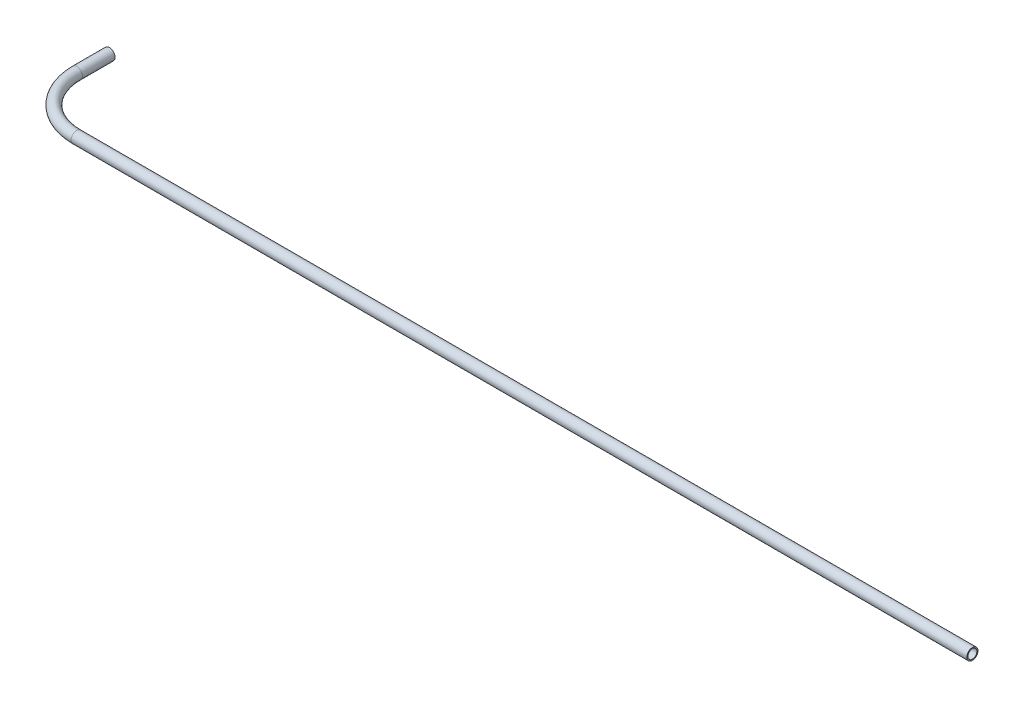
SolidWorks part; units mm, degrees
ref_plane "Front Plane" through (0, 0, 0) normal (0, 0, 1) x (1, 0, 0)
ref_plane "Top Plane" through (0, 0, 0) normal (0, 1, 0) x (1, 0, 0)
ref_plane "Right Plane" through (0, 0, 0) normal (1, 0, 0) x (0, 0, -1)
ref_axis "Axis1" through (-5.3297, 0, 0) along (1, 0, 0)
sketch "Sketch1" plane through (0, 0, 0) normal (1, 0, 0) x (0, 0, -1)
  circle A0 centre (0, 0) radius 0.2032
  circle A1 centre (0, 0) radius 0.254
  dimension "D1" = 0.4064
  dimension "D2" = 0.508
extrude "Boss-Extrude1" add sketch "Sketch1" along normal blind 40
sketch "Sketch3" plane through (-24.7302, 0, -3.0351) normal (0, -1, 0) x (-1, 0, 0)
  line L0 (-24.7302, -3.2891) -> (-24.7302, -2.7811) construction
  line L2 (-24.7302, -3.0351) -> (-24.313, -3.0351)
  line L3 (-21.813, -0.5351) -> (-21.813, 0.9409)
  arc A0 (-21.813, -0.5351) -> (-24.313, -3.0351) centre (-24.313, -0.5351) cw
  dimension "D1" = 2.5
sketch "Sketch4" plane through (0, 0, 0) normal (-1, 0, 0) x (0, 0, 1)
  circle A0 centre (0, 0) radius 0.254 construction
  circle A1 centre (0, 0) radius 0.2032 construction
  circle A2 centre (0, 0) radius 0.254
  circle A3 centre (0, 0) radius 0.2032
sweep "Sweep1" add profiles "Sketch4" path "Sketch3"
equation "\"Do\"=8.5mm"
equation "\"Lo\"=10"
equation "\"screw_diam\" = 3.5mm"
equation "\"wheel_Do\"=12.5mm"
equation "\"wheel_thickness\"=4mm"
equation "\"Collet_diameter\"=4.3"
equation "\"clearance\"= 0.5mm"
equation "\"handle_body_width\" = 10mm"
equation "\"finger_diameter\"=35"
equation "\"collet_lid_diameter\"=10"
equation "\"screw_cap_diam\"=5.15"
equation "\"handle_thickness\"=12.5mm"
equation "\"post_hole_diam\"=2"
equation "\"roll_rod_diam\"= 6.5 "
equation "\"roll_rod_length\"=6.6"
equation "\"disc_diam\"=5"
equation "\"disc_width\"=1.5"
equation "\"arm_width\"=5"
equation "\"arm_thickness\"=4.5"
equation "\"wheel_total_diam\"=30"
equation "\"spring_diam\"=4.1"
equation "\"collet_length\" = 18.75mm"
equation "\"tip_length\" = 40mm"
equation "\"D1@Boss-Extrude1\"=\"tip_length\""
equation "\"cable_tube_OD\"=0.508"
equation "\"D2@Sketch1\"=\"cable_tube_OD\""
